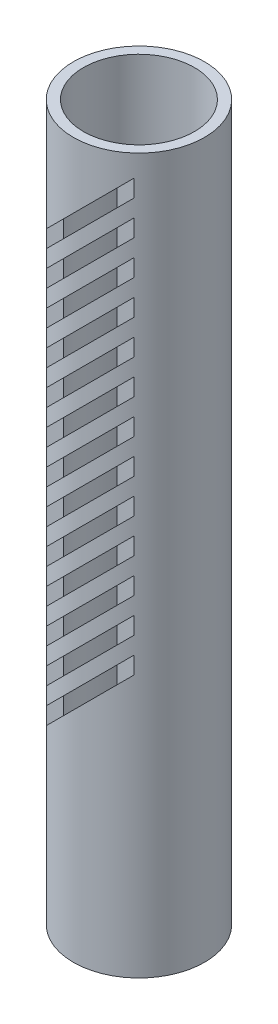
SolidWorks part; units mm, degrees
material "PBT General Purpose"
ref_plane "Front Plane" through (0, 0, 0) normal (0, 0, 1) x (1, 0, 0)
ref_plane "Top Plane" through (0, 0, 0) normal (0, 1, 0) x (1, 0, 0)
ref_plane "Right Plane" through (0, 0, 0) normal (1, 0, 0) x (0, 0, -1)
sketch "Sketch1" plane through (0, 0, 0) normal (0, 1, 0) x (1, 0, 0)
  circle A0 centre (0, 0) radius 25.654
  circle A1 centre (0, 0) radius 21.717
  dimension "D1" = 51.308
  dimension "D2" = 43.434
extrude "Boss-Extrude1" add sketch "Sketch1" along normal blind 279.4
ref_axis "Axis1" through (0, 279.4, 0) along (0, -1, 0)
sketch "Sketch2" plane through (0, 0, 0) normal (0, 0, 1) x (1, 0, 0)
  line L0 (25.654, 279.4) -> (-25.654, 279.4) construction
  line L1 (0, 0) -> (0, 279.4) construction
  line L3 (-29.0216, 224.7244) -> (-25.654, 221.3568)
  line L4 (-25.654, 221.3568) -> (29.0216, 276.0324)
  line L5 (29.0216, 276.0324) -> (25.654, 279.4)
  line L6 (25.654, 279.4) -> (-29.0216, 224.7244)
  line L7 (-25.654, 279.4) -> (-25.654, 0) construction
  line L10 (25.654, 0) -> (25.654, 279.4) construction
  dimension "D1" = 45
  dimension "D2" = 4.7625
  dimension "D4" = 0
extrude "Cut-Extrude1" cut sketch "Sketch2" along normal blind 12.7 from offset 19.05
pattern_linear "LPattern1" count 13 spacing 13.462 along (0, -1, 0) of "Cut-Extrude1"
sketch "Sketch3" plane through (0, 0, 0) normal (0, -1, 0) x (1, 0, 0)
  line L0 (0, 0) -> (-17.1821, 19.05) construction
  line L1 (0, 0) -> (17.1821, 19.05) construction
  dimension "D1" = 84.098
sketch "Sketch5" plane through (0, 279.4, 0) normal (0, 1, 0) x (1, 0, 0)
  circle A0 centre (0, 0) radius 22.86
  dimension "D1" = 45.72
extrude "Cut-Extrude3" [suppressed] cut sketch "Sketch5" against normal blind 5.08 contours A0
